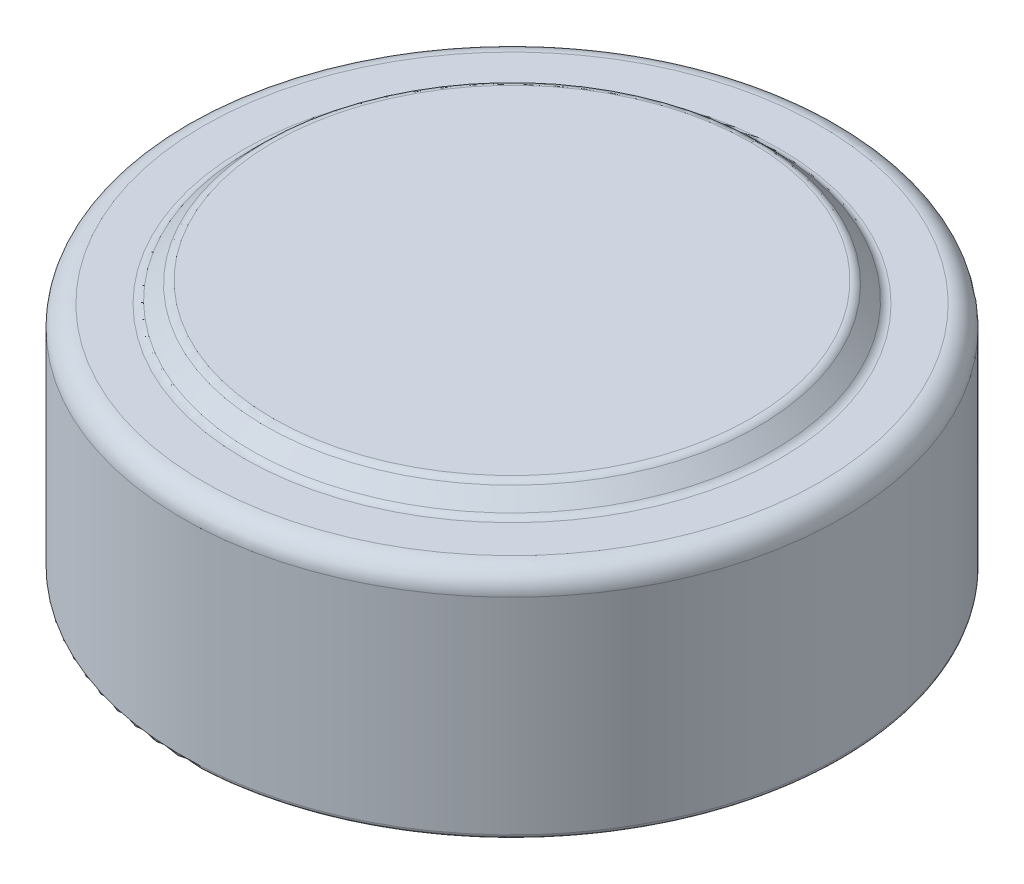
SolidWorks part; units mm, degrees
ref_plane "Front Plane" through (0, 0, 0) normal (0, 0, 1) x (1, 0, 0)
ref_plane "Top Plane" through (0, 0, 0) normal (0, 1, 0) x (1, 0, 0)
ref_plane "Right Plane" through (0, 0, 0) normal (1, 0, 0) x (0, 0, -1)
sketch "Sketch1" plane through (0, 0, 0) normal (0, 0, 1) x (1, 0, 0)
  line L0 (0, 0) -> (-7.7, 0)
  line L1 (-7.8, 0.1) -> (-7.8, 4.97)
  line L2 (-5.6564, 5.95) -> (0, 5.95)
  line L3 (0, 5.95) -> (0, 0)
  line L4 (-5.8332, 5.8768) -> (-6.1668, 5.5432)
  line L7 (-7.3, 5.47) -> (-6.3436, 5.47)
  arc A0 (-7.8, 4.97) -> (-7.3, 5.47) centre (-7.3, 4.97) cw
  arc A1 (-5.8332, 5.8768) -> (-5.6564, 5.95) centre (-5.6564, 5.7) cw
  arc A2 (-6.3436, 5.47) -> (-6.1668, 5.5432) centre (-6.3436, 5.72) ccw
  arc A3 (-7.7, 0) -> (-7.8, 0.1) centre (-7.7, 0.1) cw
  point P9 (-7.8, 5.47)
  point P14 (-5.76, 5.95)
  point P17 (-7.8, 0)
  point P18 (-6.24, 5.47)
  dimension "D6" = 0.5
  dimension "D7" = 0.25
  dimension "D8" = 0.1
  dimension "D1" = 7.8
  dimension "D2" = 5.95
  dimension "D3" = 6.24
  dimension "D4" = 5.47
  dimension "D5" = 45
revolve "Revolve1" add sketch "Sketch1" angle 360 about L3
sketch "Sketch2" plane through (0, 0, 0) normal (0, -1, 0) x (1, 0, 0)
  line L0 (0.25, 0.25) -> (2, 0.25)
  line L1 (-0.25, 2) -> (0.25, 2)
  line L2 (-0.25, 2) -> (-0.25, 0.25)
  line L3 (-0.25, -2) -> (0.25, -2)
  line L4 (0.25, 2) -> (0.25, 0.25)
  line L5 (-2, 0.25) -> (-0.25, 0.25)
  line L6 (-2, 0.25) -> (-2, -0.25)
  line L7 (-2, -0.25) -> (-0.25, -0.25)
  line L8 (2, 0.25) -> (2, -0.25)
  line L9 (0.25, -0.25) -> (2, -0.25)
  line L10 (0.25, -0.25) -> (0.25, -2)
  line L11 (-0.25, -0.25) -> (-0.25, -2)
  circle A0 centre (0, 0) radius 5.5 construction
  text T0 "                                             LR9" font "Century Gothic" height 1
  dimension "D1" = 11
  dimension "D2" = 0.5
  dimension "D3" = 0.25
  dimension "D4" = 0.25
  dimension "D5" = 0.5
  dimension "D6" = 4
  dimension "D7" = 2
  dimension "D8" = 2
  dimension "D9" = 4
wrap "Wrap1" sketch "Sketch2" wrap type scribe source sketch "Sketch2" face at (-7.7, 0, 0)
